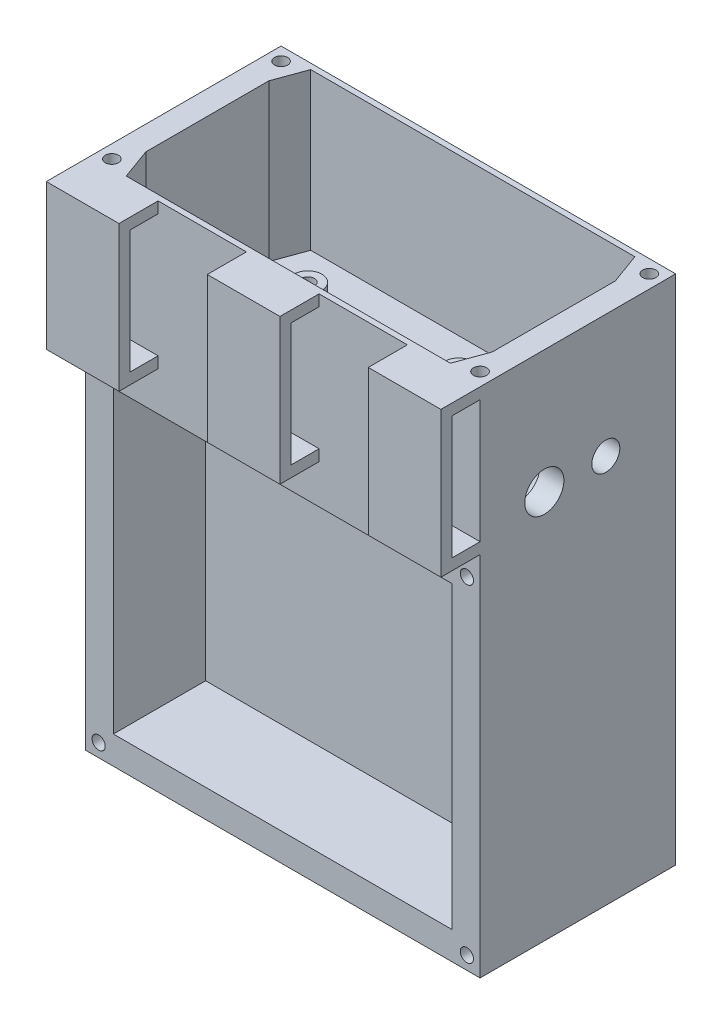
SolidWorks part; units mm, degrees
ref_plane "Front Plane" through (0, 0, 0) normal (0, 0, 1) x (1, 0, 0)
ref_plane "Top Plane" through (0, 0, 0) normal (0, 1, 0) x (1, 0, 0)
ref_plane "Right Plane" through (0, 0, 0) normal (1, 0, 0) x (0, 0, -1)
sketch "Sketch1" plane through (0, 0, 0) normal (0, 1, 0) x (1, 0, 0)
  line L1 (0, 0) -> (89.662, 0)
  line L2 (0, 0) -> (0, 44.45)
  line L3 (0, 44.45) -> (89.662, 44.45)
  line L4 (89.662, 0) -> (89.662, 44.45)
  dimension "D1" = 89.662
  dimension "D2" = 44.45
extrude "Boss-Extrude1" add sketch "Sketch1" along normal blind 80.772
sketch "Sketch2" plane through (0, 0, 0) normal (0, 0, 1) x (1, 0, 0)
  line L0 (0, 80.772) -> (0, 0) construction
  line L1 (6.35, 6.35) -> (83.312, 6.35)
  line L2 (6.35, 6.35) -> (6.35, 74.422)
  line L3 (6.35, 74.422) -> (83.312, 74.422)
  line L4 (83.312, 6.35) -> (83.312, 74.422)
  line L5 (89.662, 80.772) -> (89.662, 0) construction
  line L6 (0, 0) -> (89.662, 0) construction
  line L7 (0, 80.772) -> (89.662, 80.772) construction
  dimension "D1" = 6.35
  dimension "D2" = 6.35
  dimension "D3" = 6.35
  dimension "D4" = 6.35
extrude "Cut-Extrude1" cut sketch "Sketch2" against normal blind 20.955
sketch "Sketch3" plane through (0, 0, -44.45) normal (0, 0, -1) x (-1, 0, 0)
  line L1 (-83.312, 6.35) -> (-6.35, 6.35)
  line L2 (-83.312, 6.35) -> (-83.312, 74.422)
  line L3 (-83.312, 74.422) -> (-6.35, 74.422)
  line L4 (-6.35, 6.35) -> (-6.35, 74.422)
  line L8 (0, 80.772) -> (0, 0) construction
  line L9 (-89.662, 0) -> (0, 0) construction
  line L10 (-89.662, 80.772) -> (-89.662, 0) construction
  line L11 (-89.662, 80.772) -> (0, 80.772) construction
  dimension "D1" = 6.35
  dimension "D2" = 6.35
  dimension "D3" = 6.35
  dimension "D4" = 6.35
extrude "Cut-Extrude2" cut sketch "Sketch3" against normal blind 20.955
sketch "Sketch4" plane through (0, 80.772, 0) normal (0, 1, 0) x (1, 0, 0)
  line L1 (0, 0) -> (89.662, 0)
  line L2 (0, 0) -> (0, 44.45)
  line L3 (0, 44.45) -> (89.662, 44.45)
  line L4 (89.662, 0) -> (89.662, 44.45)
  line L5 (5.461, 1.27) -> (84.201, 1.27)
  line L6 (5.461, 1.27) -> (5.461, 43.18)
  line L7 (5.461, 43.18) -> (84.201, 43.18)
  line L8 (84.201, 1.27) -> (84.201, 43.18)
  dimension "D1" = 5.461
  dimension "D2" = 1.27
  dimension "D3" = 5.461
  dimension "D4" = 1.27
extrude "Boss-Extrude2" add sketch "Sketch4" along normal blind 35.56
sketch "Sketch5" plane through (0, 80.772, 0) normal (0, 1, 0) x (1, 0, 0)
  line L0 (0, 0) -> (89.662, 0) construction
  line L2 (5.461, 43.18) -> (5.461, 1.27) construction
  circle A0 centre (18.161, 12.065) radius 3.175
  circle A1 centre (18.161, 12.065) radius 1.5
  circle A2 centre (18.161, 32.385) radius 3.175
  circle A3 centre (18.161, 32.385) radius 1.5
  circle A4 centre (52.451, 32.385) radius 3.175
  circle A5 centre (52.451, 32.385) radius 1.5
  circle A6 centre (52.451, 12.065) radius 3.175
  circle A7 centre (52.451, 12.065) radius 1.5
  dimension "D4" = 6.35
  dimension "D5" = 6.35
  dimension "D6" = 6.35
  dimension "D7" = 6.35
  dimension "D8" = 3
  dimension "D9" = 3
  dimension "D10" = 3
  dimension "D11" = 3
  dimension "D1" = 20.32
  dimension "D2" = 12.065
  dimension "D3" = 34.29
  dimension "D12" = 12.7
extrude "Boss-Extrude3" add sketch "Sketch5" along normal blind 4.191
extrude "Cut-Extrude3" cut sketch "Sketch5<2>" against normal up to next contours A1 | A3 | A5 | A7 region at (18.161, 80.772, -12.065) region at (18.161, 80.772, -32.385) region at (52.451, 80.772, -32.385) region at (52.451, 80.772, -12.065)
sketch "Sketch5<2>" plane through (0, 80.772, 0) normal (0, 1, 0) x (1, 0, 0) same geometry as "Sketch5"
chamfer "Chamfer1" distance 6.985 angle 20 4 edges at (84.201, 98.552, -1.27) (84.201, 98.552, -43.18) (5.461, 98.552, -1.27) (5.461, 98.552, -43.18) first distance on face at (84.201, 98.552, -22.225) first distance on face at (5.461, 98.552, -22.225)
sketch "Sketch6" plane through (0, 116.332, 0) normal (0, 1, 0) x (1, 0, 0)
  line L0 (0, 0) -> (89.662, 0) construction
  line L1 (89.662, 44.45) -> (0, 44.45) construction
  line L2 (89.662, 0) -> (89.662, 44.45) construction
  line L3 (0, 44.45) -> (0, 0) construction
  circle A0 centre (3, 3) radius 1.5
  circle A1 centre (3, 41.45) radius 1.5
  circle A2 centre (86.662, 41.45) radius 1.5
  circle A3 centre (86.662, 3) radius 1.5
  dimension "D1" = 3
  dimension "D2" = 3
  dimension "D3" = 3
  dimension "D4" = 3
  dimension "D5" = 3
  dimension "D6" = 3
  dimension "D7" = 3
  dimension "D8" = 3
extrude "Cut-Extrude4" cut sketch "Sketch6" against normal blind 19.05
sketch "Sketch7" plane through (0, 0, 0) normal (0, 0, 1) x (1, 0, 0)
  line L0 (0, 0) -> (89.662, 0) construction
  line L2 (0, 116.332) -> (0, 0) construction
  line L3 (89.662, 116.332) -> (89.662, 0) construction
  line L4 (83.312, 74.422) -> (6.35, 74.422) construction
  circle A0 centre (3, 77.422) radius 1.5
  circle A1 centre (3, 3) radius 1.5
  circle A2 centre (86.662, 3) radius 1.5
  circle A3 centre (86.662, 77.422) radius 1.5
  dimension "D1" = 3
  dimension "D2" = 3
  dimension "D3" = 3
  dimension "D4" = 3
  dimension "D5" = 3
  dimension "D6" = 3
  dimension "D7" = 3
  dimension "D8" = 3
extrude "Cut-Extrude5" cut sketch "Sketch7" against normal through all
sketch "Sketch8" plane through (0, 80.772, 0) normal (0, 1, 0) x (1, 0, 0)
  line L1 (6.35, 27.305) -> (14.605, 27.305)
  line L2 (6.35, 27.305) -> (6.35, 23.495)
  line L3 (6.35, 23.495) -> (14.605, 23.495)
  line L4 (14.605, 27.305) -> (14.605, 23.495)
  line L5 (5.461, 36.195) -> (5.461, 8.255) construction
  line L8 (6.35, 23.495) -> (83.312, 23.495) construction
  line L10 (6.35, 17.145) -> (14.605, 17.145)
  line L11 (6.35, 17.145) -> (6.35, 20.955)
  line L12 (6.35, 20.955) -> (14.605, 20.955)
  line L13 (14.605, 17.145) -> (14.605, 20.955)
  dimension "D1" = 3.81
  dimension "D2" = 0.889
  dimension "D3" = 8.255
  dimension "D4" = 3.81
  dimension "D5" = 2.54
  dimension "D6" = 8.255
  dimension "D7" = 0.889
extrude "Cut-Extrude6" cut sketch "Sketch8" against normal up to surface (6.35 mm away) up to face at (52.451, 74.422, -30.885)
sketch "Sketch9" plane through (84.201, 0, 0) normal (-1, 0, 0) x (0, 0, 1)
  line L0 (-8.255, 80.772) -> (-36.195, 80.772) construction
  line L1 (-36.195, 116.332) -> (-36.195, 80.772) construction
  circle A0 centre (-28.575, 88.392) radius 3.175
  circle A1 centre (-14.605, 88.392) radius 4.445
  dimension "D1" = 6.35
  dimension "D4" = 8.89
  dimension "D2" = 7.62
  dimension "D3" = 7.62
  dimension "D5" = 13.97
extrude "Cut-Extrude7" cut sketch "Sketch9" against normal through all
sketch "Sketch10" plane through (0, 0, 0) normal (0, 0, 1) x (1, 0, 0)
  line L0 (0, 116.332) -> (89.662, 116.332) construction
  line L1 (0, 116.332) -> (16.51, 116.332)
  line L2 (0, 116.332) -> (0, 83.312)
  line L3 (0, 83.312) -> (16.51, 83.312)
  line L4 (16.51, 116.332) -> (16.51, 83.312)
  line L5 (89.662, 116.332) -> (73.152, 116.332)
  line L6 (89.662, 116.332) -> (89.662, 83.312)
  line L7 (89.662, 83.312) -> (73.152, 83.312)
  line L8 (73.152, 116.332) -> (73.152, 83.312)
  line L9 (36.576, 116.332) -> (53.086, 116.332)
  line L10 (36.576, 116.332) -> (36.576, 83.312)
  line L11 (36.576, 83.312) -> (53.086, 83.312)
  line L12 (53.086, 116.332) -> (53.086, 83.312)
  dimension "D1" = 16.51
  dimension "D2" = 16.51
  dimension "D3" = 16.51
  dimension "D4" = 20.066
  dimension "D5" = 33.02
extrude "Boss-Extrude4" add sketch "Sketch10" along normal blind 8.89
sketch "Sketch11" plane through (0, 0, 0) normal (-1, 0, 0) x (0, 0, 1)
  line L0 (8.89, 116.332) -> (8.89, 83.312) construction
  line L1 (6.35, 113.792) -> (0, 113.792)
  line L2 (6.35, 113.792) -> (6.35, 85.852)
  line L3 (6.35, 85.852) -> (0, 85.852)
  line L4 (0, 113.792) -> (0, 85.852)
  line L5 (8.89, 83.312) -> (0, 83.312) construction
  line L6 (-44.45, 116.332) -> (8.89, 116.332) construction
  line L7 (0, 83.312) -> (0, 0) construction
  dimension "D1" = 2.54
  dimension "D2" = 2.54
  dimension "D3" = 2.54
extrude "Cut-Extrude8" cut sketch "Sketch11" against normal through all
